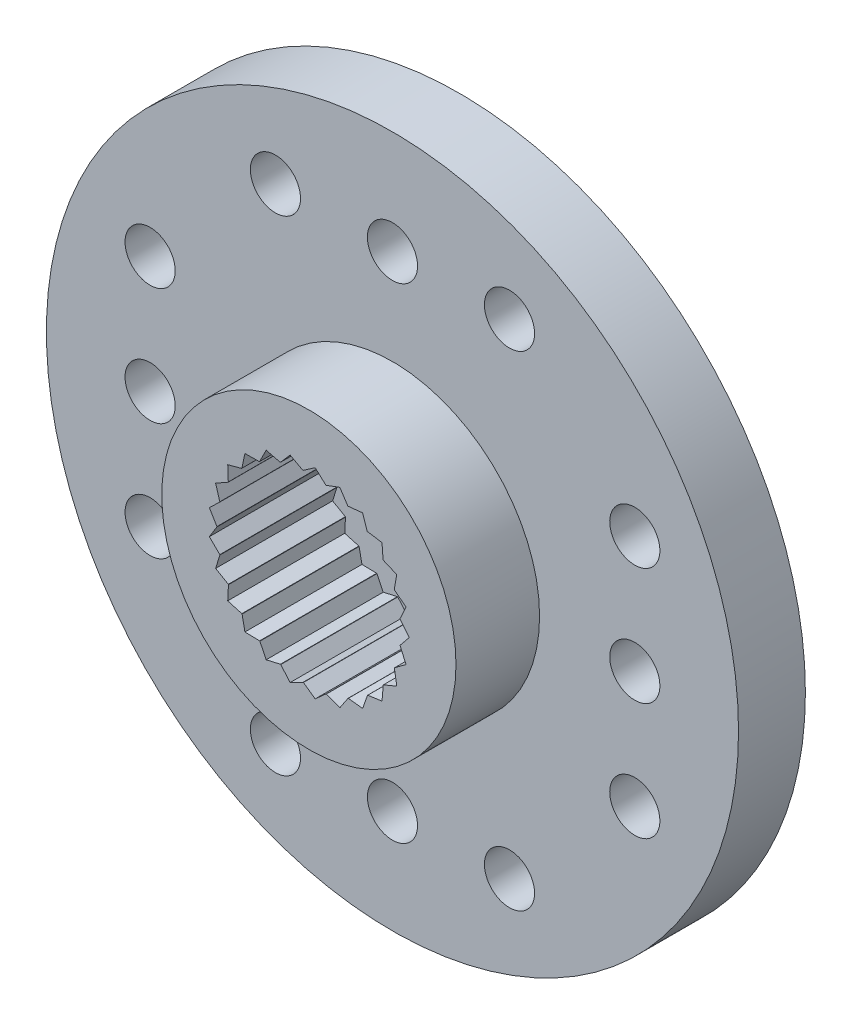
SolidWorks part; units mm, degrees
ref_plane "Front Plane" through (0, 0, 0) normal (0, 0, 1) x (1, 0, 0)
ref_plane "Top Plane" through (0, 0, 0) normal (0, 1, 0) x (1, 0, 0)
ref_plane "Right Plane" through (0, 0, 0) normal (1, 0, 0) x (0, 0, -1)
sketch "Sketch1" plane through (0, 0, 0) normal (0, 0, 1) x (1, 0, 0)
  line L0 (0, 7.2478) -> (0, 0) construction
  circle A0 centre (0, 0) radius 10.35
  circle A6 centre (0, 0) radius 4.4
  circle A9 centre (0, 0) radius 7.2478 construction
  circle A10 centre (0, 7.2478) radius 0.75
  circle A20 centre (3.5, 7.2478) radius 0.75
  circle A21 centre (-3.5, 7.2478) radius 0.75
  dimension "D1" = 20.7
  dimension "D2" = 3.5
  dimension "D4" = 8.8
  dimension "D3" = 1.5
  dimension "D5" = 14.4955
  dimension "D6" = 14.4955
extrude "Boss-Extrude1" add sketch "Sketch1" along normal blind 2
pattern_circular "CirPattern2" count 4 over 360 about axis through (0, 0, 2) along (0, 0, -1) reverse direction yes of face at (4.25, 7.2478, 2) of face at (0.75, 7.2478, 2) of face at (-2.75, 7.2478, 2)
extrude "Boss-Extrude2" add sketch "Sketch1<2>" along normal blind 4.5 contours A6 region at (0, 0, 0)
sketch "Sketch1<2>" plane through (0, 0, 0) normal (0, 0, 1) x (1, 0, 0) same geometry as "Sketch1"
sketch "Sketch2" plane through (0, 0, 0) normal (0, 0, -1) x (-1, 0, 0)
  circle A0 centre (0, 0) radius 1.5
extrude "Cut-Extrude1" cut sketch "Sketch2" against normal blind 4.5
sketch "Sketch3" plane through (0, 0, 4.5) normal (0, 0, 1) x (1, 0, 0)
  circle A0 centre (0, 0) radius 2.75
extrude "Cut-Extrude2" cut sketch "Sketch3" against normal blind 3.5
sketch "Sketch4" plane through (0, 0, 4.5) normal (0, 0, 1) x (1, 0, 0)
  line L0 (0, 0) -> (-3, 0)
  line L1 (0, 0) -> (-2.9763, 0.376)
  line L2 (0, 0) -> (-2.9083, 0.7359)
  line L3 (-2.75, 0) -> (-2.9763, 0.376)
  line L4 (-2.666, 0.6746) -> (-2.9763, 0.376)
  circle A0 centre (0, 0) radius 3
  circle A1 centre (0, 0) radius 2.75 construction
  circle A2 centre (0, 0) radius 2.75 construction
  circle A3 centre (0, 0) radius 2.75
  circle M6 centre (0, 0) radius 2.75
  dimension "D1" = 7.2
  dimension "D2" = 14.2
extrude "Cut-Extrude3" cut sketch "Sketch4" against normal blind 3.5 contours L4 L1 M6 | L3 L1 M6 region at (-2.8205, 0.2422, 4.5) region at (-2.7928, 0.4638, 4.5)
pattern_circular "CirPattern1" count 25 over 360 about axis through (0, 0, 4.5) along (0, 0, -1) of "Cut-Extrude3" reverse direction yes
ref_plane "Plane1" through (0, 0, 19) normal (0, 0, -1) x (-1, 0, 0)
ref_plane "Plane2" through (0, 0, 16.5) normal (0, 0, -1) x (-1, 0, 0)
